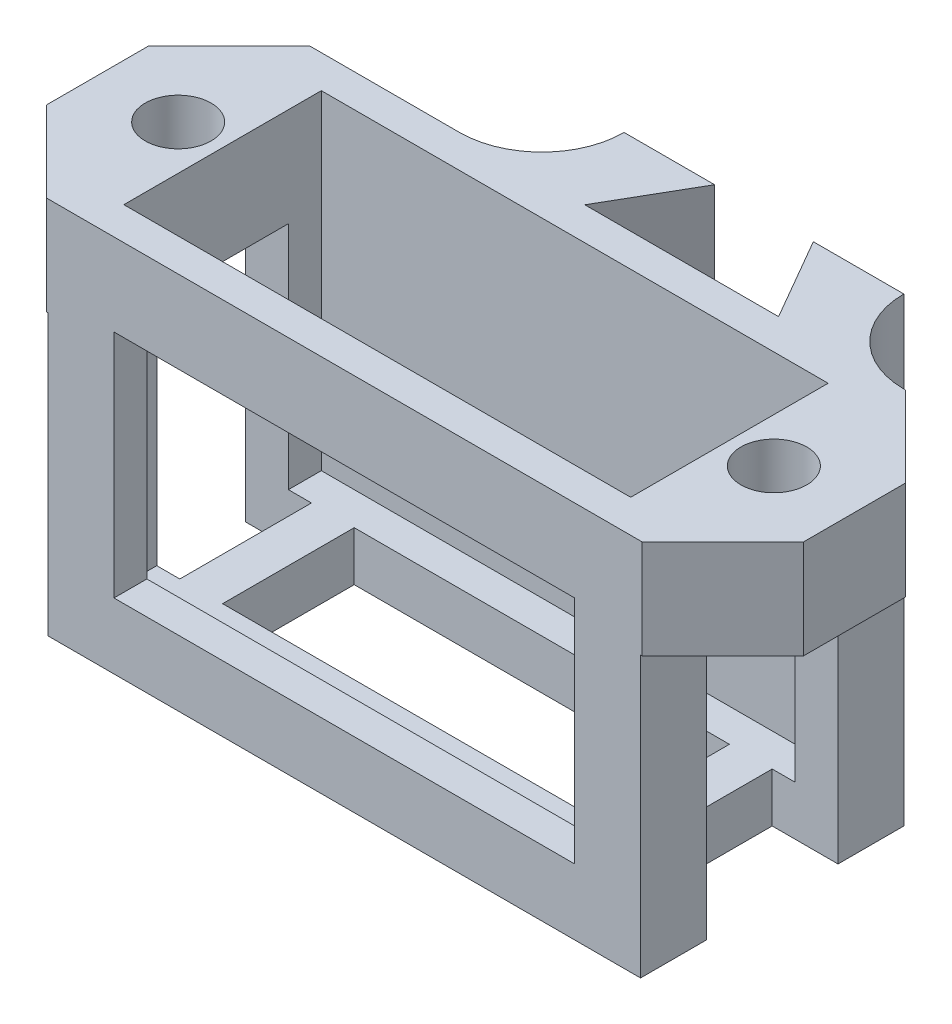
SolidWorks part; units mm, degrees
note: The reader was unsure of these and kept them because the rebuilt part matched: shared geometry of "Sketch3<3>", "Sketch2<3>".
ref_plane "Front Plane" through (0, 0, 0) normal (0, 0, 1) x (1, 0, 0)
ref_plane "Top Plane" through (0, 0, 0) normal (0, 1, 0) x (1, 0, 0)
ref_plane "Right Plane" through (0, 0, 0) normal (1, 0, 0) x (0, 0, -1)
sketch "Sketch1" plane through (0, 0, 0) normal (0, 0, 1) x (1, 0, 0)
  line L0 (-15, 15) -> (15, 15)
  line L1 (15, 15) -> (15, -15)
  line L2 (15, -15) -> (-15, -15)
  line L3 (-15, -15) -> (-15, 15)
  line L4 (-15, 0) -> (15, 0) construction
  line L5 (-15, 5) -> (-23, 5)
  line L6 (-23, 5) -> (-23, -1)
  line L7 (-23, -1) -> (-18, -1)
  line L8 (-18, -1) -> (-18, -18)
  line L9 (-18, -18) -> (18, -18)
  line L10 (18, -18) -> (18, -1)
  line L11 (18, -1) -> (23, -1)
  line L12 (23, -1) -> (23, 5)
  line L13 (23, 5) -> (15, 5)
  line L14 (-15, 5) -> (15, 5)
  point P6 (0, 0)
  dimension "D1" = 30
  dimension "D2" = 30
  dimension "D3" = 20
  dimension "D4" = 3
  dimension "D5" = 3
  dimension "D6" = 5
  dimension "D7" = 6
extrude "Extrude1" add sketch "Sketch1" along normal mid plane 16 contours L12 L13 L1 L2 L3 L5 L6 L7 L8 L9 L10 L11 | L4 L3 L2 L1 | L3 L4 L1 L14
sketch "Sketch2" plane through (0, 0, 0) normal (0, 1, 0) x (1, 0, 0)
  line L0 (-15.4, 0) -> (15.4, 0) construction
  line L1 (0, -6) -> (0, 6) construction
  line L2 (-15.4, -6) -> (-15.4, 6)
  line L3 (-15.4, 6) -> (15.4, 6)
  line L4 (15.4, 6) -> (15.4, -6)
  line L5 (15.4, -6) -> (-15.4, -6)
  line L6 (-18.1, 0) -> (-15.4, 0) construction
  line L7 (15.4, 0) -> (18.1, 0) construction
  line L8 (23, -3.1) -> (18.1, -8)
  line L9 (23, -8) -> (23, 8) construction
  line L11 (23, -8) -> (-23, -8) construction
  line L12 (18.1, -8) -> (23, -8)
  line L14 (23, -8) -> (23, -3.1)
  line L15 (18.1, 8) -> (23, 3.1)
  line L17 (23, 8) -> (-23, 8) construction
  line L18 (23, 3.1) -> (23, 8)
  line L20 (23, 8) -> (18.1, 8)
  line L21 (-18.1, 8) -> (-23, 3.1)
  line L22 (-23, -8) -> (-23, 8) construction
  line L23 (-23, 3.1) -> (-23, 8)
  line L24 (-23, 8) -> (-18.1, 8)
  line L25 (-23, -3.1) -> (-18.1, -8)
  line L26 (-18.1, -8) -> (-23, -8)
  line L27 (-23, -8) -> (-23, -3.1)
  line L28 (-11.4, 4) -> (11.4, 4)
  line L29 (-11.4, 4) -> (-11.4, -4)
  line L30 (-11.4, -4) -> (11.4, -4)
  line L31 (11.4, -4) -> (11.4, 4)
  circle A0 centre (-18.1, 0) radius 2
  circle A1 centre (18.1, 0) radius 2
  point P2 (0, 0)
  point P6 (0, 0)
  point P46 (-11.4, 0)
  point P47 (11.4, 0)
  dimension "D4" = 4
  dimension "D1" = 12
  dimension "D2" = 30.8
  dimension "D3" = 36.2
  dimension "D5" = 2
  dimension "D6" = 4
  dimension "D7" = 4
extrude "Extrude2" cut sketch "Sketch2" against normal blind 20 from surface at 5 contours L27 L26 L25 | A0 | L24 L23 L21 | L30 L31 L28 L29 | L5 L4 L3 L2 L31 L30 L29 L28 | L18 L20 L15 | A1 | L12 L14 L8 starting at face at (0, 5, 0)
sketch "Sketch3" [suppressed]
  line L0 (-14, -14) -> (14, -14)
  line L1 (14, -14) -> (14, 0)
  line L2 (14, 0) -> (-14, 0)
  line L3 (-18, -1) -> (-14, -1)
  line L4 (-14, 0) -> (-14, -14)
  line L5 (-18, -18) -> (18, -18) construction
  line L6 (18, -18) -> (18, -1) construction
  line L7 (-18, -1) -> (-18, -18) construction
  line L8 (-15, 5) -> (15, 5) construction
  line L9 (18, -1) -> (14, -1)
  line L10 (-18, -1) -> (-18, -18) construction
  line L11 (-18, -1) -> (-18, -18)
  line L12 (-18, -18) -> (-14, -18)
  line L13 (-18, -18) -> (18, -18) construction
  line L14 (-14, -18) -> (-14, -14)
  line L16 (18, -18) -> (18, -1) construction
  line L17 (18, -1) -> (18, -18)
  line L18 (18, -18) -> (14, -18)
  line L19 (14, -18) -> (14, -14)
  dimension "D1" = 4
  dimension "D2" = 4
  dimension "D3" = 4
  dimension "D4" = 5
sketch "Sketch3<3>" plane through (0, 0, 0) normal (0, 0, 1) x (1, 0, 0) same geometry as "Sketch3"
extrude "Extrude3" cut sketch "Sketch3" against normal up to surface (14 mm away) from surface
extrude "Extrude4" cut sketch "Sketch3<3>" against normal mid plane 8 contours L2 L4 L0 L1
extrude "Extrude5" cut sketch "Sketch2<3>" against normal up to surface (3 mm away) from surface at -15 contours L30 L31 L28 L29 up to face at (0, -18, 0) starting at face at (0, -15, 0)
sketch "Sketch2<3>" plane through (0, 0, 0) normal (0, 1, 0) x (1, 0, 0) same geometry as "Sketch2"
sketch "Sketch4" plane through (0, 0, 0) normal (0, 1, 0) x (1, 0, 0)
  line L0 (13, 8) -> (13, 13)
  line L1 (13, 13) -> (7.5, 13)
  line L2 (7.5, 13) -> (10.3868, 8)
  line L3 (18.1, 8) -> (-18.1, 8) construction
  line L4 (-4, 8) -> (-4, 13)
  line L5 (-4, 13) -> (1.5, 13)
  line L6 (1.5, 13) -> (-1.3868, 8)
  line L7 (-1.3868, 8) -> (-9, 8)
  line L8 (10.3868, 8) -> (18, 8)
  line L9 (18.1, 8) -> (-18.1, 8) construction
  line L10 (18.1, 8) -> (-18.1, 8) construction
  arc A0 (-4, 13) -> (-9, 8) centre (-9, 13) cw
  arc A1 (13, 13) -> (18, 8) centre (18, 13) ccw
  dimension "D1" = 5
  dimension "D2" = 17
  dimension "D3" = 6
  dimension "D4" = 60
extrude "Extrude6" add sketch "Sketch4" against normal up to surface (23 mm away) from vertex
